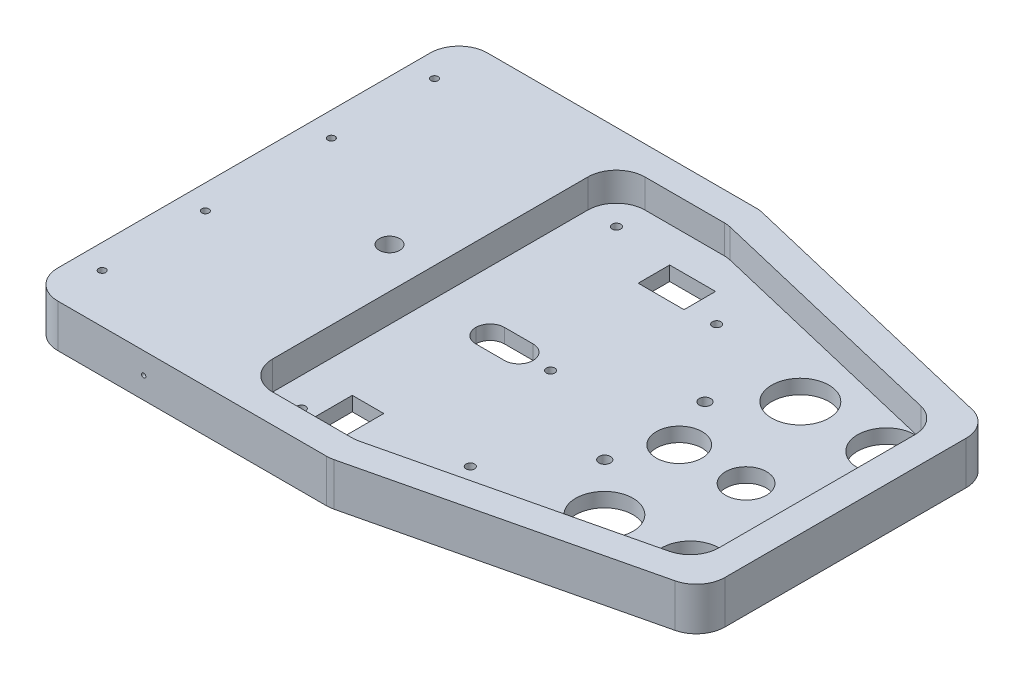
SolidWorks part; units mm, degrees
material "Carvalho"
ref_plane "Plano frontal" through (0, 0, 0) normal (0, 0, 1) x (1, 0, 0)
ref_plane "Plano superior" through (0, 0, 0) normal (0, 1, 0) x (1, 0, 0)
ref_plane "Plano direito" through (0, 0, 0) normal (1, 0, 0) x (0, 0, -1)
sketch "Esboço1" plane through (0, 0, 0) normal (0, 1, 0) x (1, 0, 0)
  line L0 (210, 50) -> (105, 75)
  line L1 (0, -75) -> (105, -75)
  line L2 (0, -75) -> (0, 75)
  line L3 (0, 75) -> (105, 75)
  line L4 (210, -50) -> (210, 50)
  line L7 (105, -75) -> (210, -50)
  line L8 (-14.8259, 0) -> (14.392, 0) construction
  line L9 (0, 21.2472) -> (0, -16.7598) construction
  circle A0 centre (50.8, 0) radius 3.5719
  circle A1 centre (175.26, 0) radius 7.14
  circle A2 centre (151.92, 0) radius 8
  circle A3 centre (151.92, 0) radius 8 construction
  circle A4 centre (8.5, -58) radius 1.25
  circle A5 centre (8.5, -22) radius 1.25
  circle A6 centre (8.5, -58) radius 2.5 construction
  circle A7 centre (8.5, -22) radius 2.5 construction
  circle A8 centre (8.5, 22) radius 1.25
  circle A9 centre (8.5, 58) radius 1.25
  point P0 (0, 0)
  dimension "D3" = 7.1437
  dimension "D5" = 14.28
  dimension "D9" = 2.5
  dimension "D1" = 25
  dimension "D2" = 150
  dimension "D4" = 50.8
  dimension "D6" = 210
  dimension "D7" = 175.26
  dimension "D8" = 105
extrude "Ressalto-extrusão1" add sketch "Esboço1" along normal blind 15
sketch "Esboço3" plane through (0, 15, 0) normal (0, 1, 0) x (1, 0, 0)
  line L0 (200, 42.1014) -> (200, -42.1014)
  line L2 (65, -65) -> (65, 65)
  line L6 (210, -50) -> (210, 50) construction
  line L7 (0, 75) -> (0, -75) construction
  line L8 (-22.821, 0) -> (224.4652, 0) construction
  line L9 (65, 65) -> (103.8259, 65)
  line L10 (103.8259, 65) -> (200, 42.1014)
  line L11 (65, -65) -> (103.8259, -65)
  line L12 (103.8259, -65) -> (200, -42.1014)
  line L13 (105, -75) -> (210, -50) construction
  line L14 (0, -75) -> (105, -75) construction
  circle M12 centre (151.92, 0) radius 8
  circle M14 centre (175.26, 0) radius 7.14
  dimension "D1" = 10
  dimension "D2" = 65
  dimension "D3" = 10
  dimension "D4" = 10
extrude "Corte-extrusão2" cut sketch "Esboço3" against normal blind 10 contours L2 L8 L0 L10 L9 M12 M14 | L8 L2 L11 L12 L0 M14 M12 region at (126.5743, 15, -29.5512) region at (126.5743, 15, 29.5512)
fillet "Filete1" radius 10 12 edges at (105, 7.5, 75) (0, 7.5, 75) (0, 7.5, -75) (210, 7.5, 50) (105, 7.5, -75) (210, 7.5, -50) (200, 10, 42.1014) (200, 10, -42.1014) (103.8259, 10, 65) (65, 10, 65) (103.8259, 10, -65) (65, 10, -65)
sketch "Esboço5" plane through (0, 0, 0) normal (0, -1, 0) x (1, 0, 0)
  line L0 (175.26, 0) -> (90.92, 0) construction
  line L2 (143.42, 17.5) -> (143.42, -17.5) construction
  line L3 (175.26, 0) -> (101.1849, 0) construction
  line L8 (80.92, -5) -> (100.92, -5)
  line L9 (80.92, -5) -> (80.92, 5)
  line L10 (80.92, 5) -> (100.92, 5)
  line L11 (100.92, -5) -> (100.92, 5)
  line L12 (80.92, -5) -> (100.92, 5) construction
  line L13 (80.92, 5) -> (100.92, -5) construction
  circle A0 centre (143.42, 17.5) radius 2
  circle A1 centre (143.42, -17.5) radius 2
  point P5 (143.42, 0)
  dimension "D6" = 4
  dimension "D1" = 35
  dimension "D2" = 42.5
  dimension "D3" = 20
  dimension "D4" = 31.84
  dimension "D5" = 10
extrude "Corte-extrusão4" cut sketch "Esboço5" against normal through all
fillet "Filete2" radius 5 4 edges at (80.92, 2.5, -5) (80.92, 2.5, 5) (100.92, 2.5, 5) (100.92, 2.5, -5)
sketch "Esboço6" plane through (0, 15, 0) normal (0, 1, 0) x (1, 0, 0)
  line L0 (224.3981, 0) -> (150.0179, 0) construction
  circle A0 centre (190, -34.2028) radius 10
  circle A1 centre (190, 34.2028) radius 10
  circle A2 centre (160, 34.2028) radius 10
  arc A3 (200, 34.2028) -> (192.3162, 43.9309) centre (190, 34.2028) ccw construction
  circle A4 centre (160, -34.2028) radius 10
  arc A5 (200, 34.2028) -> (192.3162, 43.9309) centre (190, 34.2028) ccw construction
  dimension "D3" = 30
extrude "Corte-extrusão5" cut sketch "Esboço6" against normal through all
sketch "Esboço7" plane through (0, 0, 0) normal (0, -1, 0) x (1, 0, 0)
  line L0 (-8.8077, 0) -> (220.236, 0) construction
  line L1 (65, 55) -> (65, -55) construction
  line L3 (90.9, 58.1) -> (79.9, 58.1)
  line L4 (90.9, 58.1) -> (90.9, 42.1)
  line L5 (90.9, 42.1) -> (79.9, 42.1)
  line L6 (79.9, 58.1) -> (79.9, 42.1)
  line L7 (111.9, -41.7) -> (95.9, -41.7)
  line L8 (111.9, -41.7) -> (111.9, -52.7)
  line L9 (111.9, -52.7) -> (95.9, -52.7)
  line L10 (95.9, -41.7) -> (95.9, -52.7)
  line L11 (80.4, 57.6) -> (90.4, 57.6) construction
  line L12 (80.4, 57.6) -> (80.4, 42.6) construction
  line L13 (85.4, 58.1) -> (85.4, 42.1) construction
  line L14 (96.4, -52.2) -> (96.4, -42.2) construction
  line L15 (96.4, -52.2) -> (111.4, -52.2) construction
  circle A3 centre (75, 55) radius 1.5
  circle A5 centre (122, 43) radius 1.5
  circle A6 centre (107, 0) radius 1.5
  circle A7 centre (75, -55) radius 1.5
  circle A8 centre (122, -43) radius 1.5
  dimension "D1" = 55
  dimension "D2" = 3
  dimension "D3" = 43
  dimension "D4" = 47
  dimension "D5" = 10
  dimension "D6" = 32
  dimension "D7" = 11
  dimension "D8" = 0.5
  dimension "D9" = 0.5
  dimension "D10" = 16
  dimension "D11" = 16
  dimension "D12" = 11
  dimension "D13" = 0.5
  dimension "D14" = 0.5
extrude "Corte-extrusão6" cut sketch "Esboço7" against normal through all contours A3 | A6 | A5 | A7 | A8 | L6 L5 L4 L3 | L7 L10 L9 L8
sketch "Esboço8" plane through (0, 0, 75) normal (0, 0, 1) x (1, 0, 0)
  line L0 (0, 0) -> (0, 15) construction
  line L1 (40, 15) -> (40, 0) construction
  line L2 (10, 15) -> (103.8259, 15) construction
  line L3 (10, 0) -> (103.8259, 0) construction
  circle A0 centre (40, 7.5) radius 0.75
  point P10 (40, 8.6082)
  dimension "D1" = 1.5
  dimension "D2" = 40
extrude "Corte-extrusão7" cut sketch "Esboço8" against normal through all
